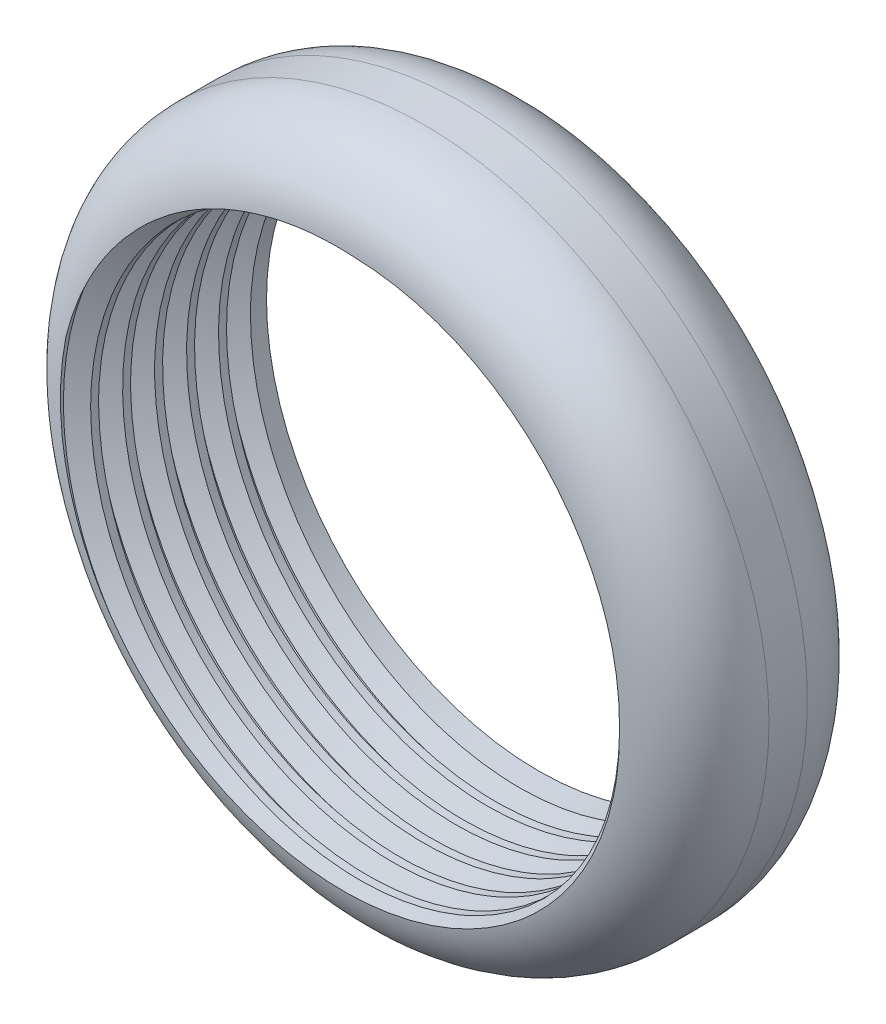
SolidWorks part; units mm, degrees
ref_plane "Front Plane" through (0, 0, 0) normal (0, 0, 1) x (1, 0, 0)
ref_plane "Top Plane" through (0, 0, 0) normal (0, 1, 0) x (1, 0, 0)
ref_plane "Right Plane" through (0, 0, 0) normal (1, 0, 0) x (0, 0, -1)
sketch "Sketch2" plane through (0, 0, 0) normal (0, 0, 1) x (1, 0, 0)
  circle A0 centre (0, 0) radius 9.017
  circle A1 centre (0, 0) radius 11.43
  dimension "D1" = 18.034
  dimension "D2" = 22.86
extrude "Boss-Extrude1" add sketch "Sketch2" along normal blind 6.35
thread "Thread1" pitch 1.0583 method cut profile "Thread Profile1" start angle 0, offset 0, length 6.35, pitch 1.0583, diameter 18.034
ref_plane "Plane1" through (9.017, 0, 0) normal (0, -1, 0) x (1, 0, 0)
sketch "Thread Profile1" plane through (9.017, 0, 0) normal (0, -1, 0) x (1, 0, 0)
  line L0 (0, 0) -> (0, 1.0583) construction
  line L1 (0, 0) -> (0.5728, 0.3307)
  line L2 (0.5728, 0.3307) -> (0.5728, 0.463)
  line L3 (0.5728, 0.463) -> (0, 0.7937)
  line L4 (0.5728, 0.3969) -> (0, 0.3969) construction
  line L11 (0, 0) -> (0, 0.7937)
  point P2 (0, 0)
  dimension "Pitch" = 1.0583
  dimension "Profile_Angle" = 60
  dimension "Profile_Land" = 0.1323
  dimension "Profile_Height" = 0.5728
fillet "Fillet1" radius 2.54 2 edges at (11.43, 0, 6.35) (11.43, 0, 0)
